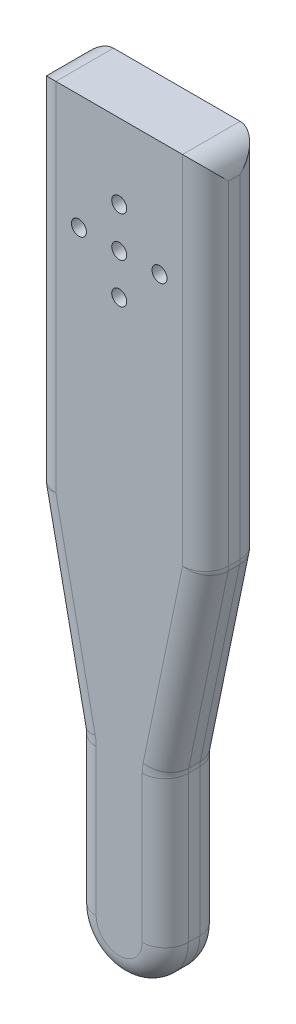
SolidWorks part; units mm, degrees
ref_plane "Front Plane" through (0, 0, 0) normal (0, 0, 1) x (1, 0, 0)
ref_plane "Top Plane" through (0, 0, 0) normal (0, 1, 0) x (1, 0, 0)
ref_plane "Right Plane" through (0, 0, 0) normal (1, 0, 0) x (0, 0, -1)
sketch "Sketch2" plane through (0, 0, 0) normal (0, 0, 1) x (1, 0, 0)
  line L1 (-29.8024, 62.3024) -> (0.1976, 62.3024)
  line L2 (-29.8024, 62.3024) -> (-29.8024, -67.6976)
  line L3 (-29.8024, -67.6976) -> (0.1976, -67.6976)
  line L4 (0.1976, 62.3024) -> (0.1976, -67.6976)
  dimension "D1" = 130
extrude "Boss-Extrude1" add sketch "Sketch2" along normal blind 10
sketch "Sketch3" plane through (0, 0, 10) normal (0, 0, 1) x (1, 0, 0)
  line L0 (-14.8024, 62.3024) -> (-14.8024, 42.3024) construction
  line L1 (0.1976, 62.3024) -> (-29.8024, 62.3024) construction
  line L4 (-29.8024, -67.6976) -> (-21.8024, -67.6976)
  line L5 (-29.8024, -67.6976) -> (-29.8024, 0)
  line L6 (-29.8024, 0) -> (-21.8024, 0)
  line L7 (-21.8024, -67.6976) -> (-21.8024, 0)
  line L9 (0, 0) -> (-7.8024, 0)
  line L10 (0, 0) -> (0, -67.6976)
  line L11 (0, -67.6976) -> (-7.8024, -67.6976)
  line L12 (-7.8024, 0) -> (-7.8024, -67.6976)
  line L13 (-29.8024, -67.6976) -> (0.1976, -67.6976) construction
  circle A0 centre (-14.8024, 42.3024) radius 7 construction
  circle A1 centre (-21.8024, 42.3024) radius 1.3
  circle A2 centre (-14.8024, 49.3024) radius 1.3
  circle A3 centre (-7.8024, 42.3024) radius 1.3
  circle A4 centre (-14.8024, 35.3024) radius 1.3
  circle A5 centre (-14.8024, 42.3024) radius 1.3
  point P5 (-21.8024, 42.3024)
  point P7 (-14.8024, 49.3024)
  point P9 (-7.8024, 42.3024)
  point P11 (-14.8024, 35.3024)
sketch "Sketch6" plane through (0, 0, 10) normal (0, 0, 1) x (1, 0, 0)
  line L1 (-29.8024, -67.6976) -> (-22.8024, -67.6976)
  line L2 (-29.8024, -67.6976) -> (-29.8024, 0)
  line L4 (-22.8024, -67.6976) -> (-22.8024, -33.8488)
  line L11 (0.1976, -67.6976) -> (-6.8024, -67.6976)
  line L12 (0.1976, -67.6976) -> (0.1976, 0)
  line L14 (-6.8024, -67.6976) -> (-6.8024, -33.8488)
  line L15 (-29.8024, 0) -> (-22.8024, -33.8488)
  line L16 (-6.8024, -33.8488) -> (0.1976, 0)
  dimension "D1" = 7
extrude "Cut-Extrude3" cut sketch "Sketch6" against normal through all contours L14 L16 L12 L11 | L4 L15 L2 L1
fillet "Fillet3" 2 edges at (-22.8024, -67.6976, 5) (-6.8024, -67.6976, 5) type full round first side face at (-22.8024, -50.7732, 5) second side face at (-6.8024, -50.7732, 5) middle face at (-14.8024, -67.6976, 5)
fillet "Fillet4" radius 4 20 edges at (-14.8024, -67.6976, 0) (-14.8024, -67.6976, 10) (-6.8024, -46.7732, 0) (-6.8024, -46.7732, 10) (-22.8024, -46.7732, 0) (-22.8024, -46.7732, 10) (0.1976, 31.1512, 10) (0.1976, 62.3024, 5) (0.1976, 31.1512, 0) (0.1976, 0, 5) (-3.3024, -16.9244, 0) (-6.8024, -33.8488, 5) (-3.3024, -16.9244, 10) (-22.8024, -33.8488, 5) (-26.3024, -16.9244, 0) (-26.3024, -16.9244, 10) (-29.8024, 31.1512, 0) (-29.8024, 62.3024, 5) (-29.8024, 31.1512, 10) (-29.8024, 0, 5)
extrude "Cut-Extrude4" cut sketch "Sketch3" against normal through all contours A1 | A4 | A3 | A2 | A5
